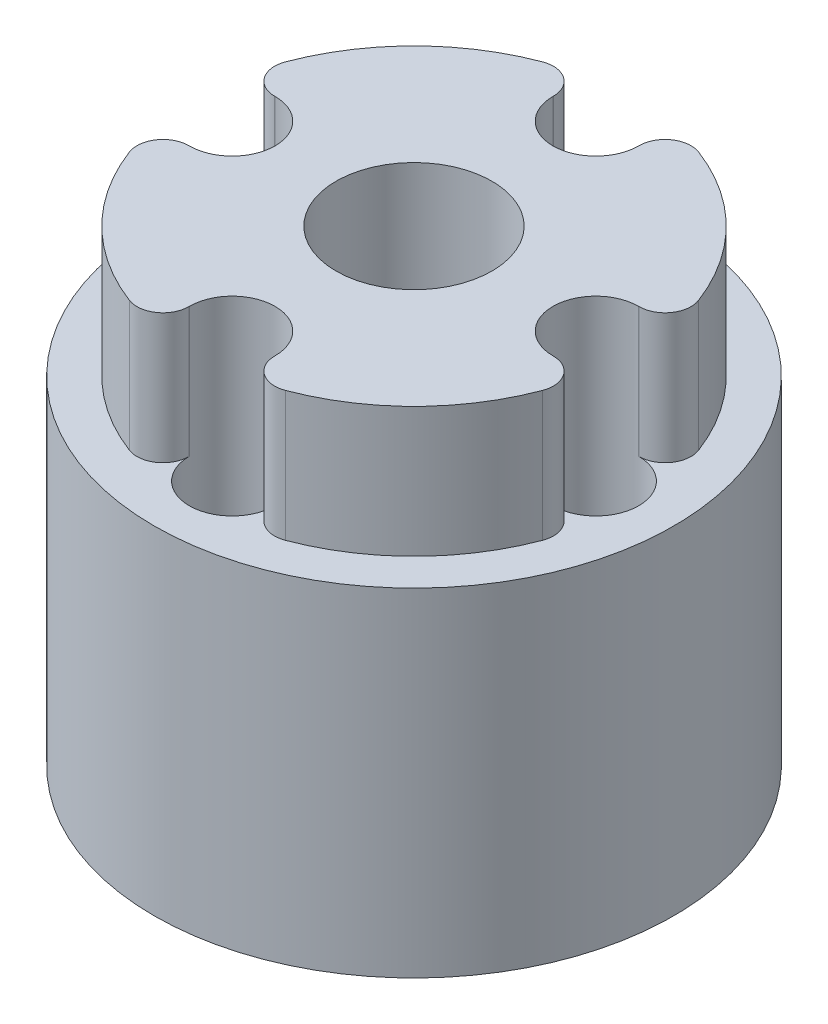
SolidWorks part; units mm, degrees
ref_plane "Спереди" through (0, 0, 0) normal (0, 0, 1) x (1, 0, 0)
ref_plane "Сверху" through (0, 0, 0) normal (0, 1, 0) x (1, 0, 0)
ref_plane "Справа" through (0, 0, 0) normal (1, 0, 0) x (0, 0, -1)
sketch "Эскиз1" plane through (0, 0, 0) normal (0, 1, 0) x (1, 0, 0)
  circle A0 centre (0, 0) radius 10
  dimension "D1" = 20
extrude "основание" add sketch "Эскиз1" along normal blind 13
sketch "Эскиз2" plane through (0, 13, 0) normal (0, 1, 0) x (1, 0, 0)
  circle A0 centre (0, 0) radius 8.5
  dimension "D1" = 17
extrude "ось" add sketch "Эскиз2" along normal blind 5
sketch "Эскиз3" plane through (0, 18, 0) normal (0, 1, 0) x (1, 0, 0)
  circle A0 centre (0, 0) radius 3
  dimension "D1" = 6
extrude "отверстие для винтика" cut sketch "Эскиз3" against normal through all
sketch "Эскиз4" plane through (0, 18, 0) normal (0, 1, 0) x (1, 0, 0)
  line L0 (-1.65, 7) -> (-1.65, 8.3383)
  line L2 (1.65, 8.3383) -> (1.65, 7)
  circle A0 centre (0, 0) radius 7 construction
  arc A1 (-1.65, 7) -> (1.65, 7) centre (0, 7) ccw
  arc A3 (1.65, 8.3383) -> (-1.65, 8.3383) centre (0, 0) ccw
  circle A4 centre (0, 0) radius 8.5 construction
  dimension "D1" = 14
  dimension "D2" = 1.65
extrude "паз для винта" cut sketch "Эскиз4" against normal up to surface (5 mm away) up to face at (0, 13, 8.5)
sketch "Эскиз5" plane through (0, 13, 0) normal (0, 1, 0) x (1, 0, 0)
  circle A0 centre (0, 7) radius 1.65
  arc A1 (-1.65, 7) -> (1.65, 7) centre (0, 7) ccw construction
extrude "сквозное отверстие для винта" cut sketch "Эскиз5" against normal through all
fillet "Скругление1" radius 1 2 edges at (-1.65, 15.5, -8.3383) (1.65, 15.5, -8.3383)
pattern_circular "Круговой массив1" count 4 over 360 about axis through (0, 0, 0) along (0, 1, 0) of "сквозное отверстие для винта", "паз для винта", "Скругление1"
